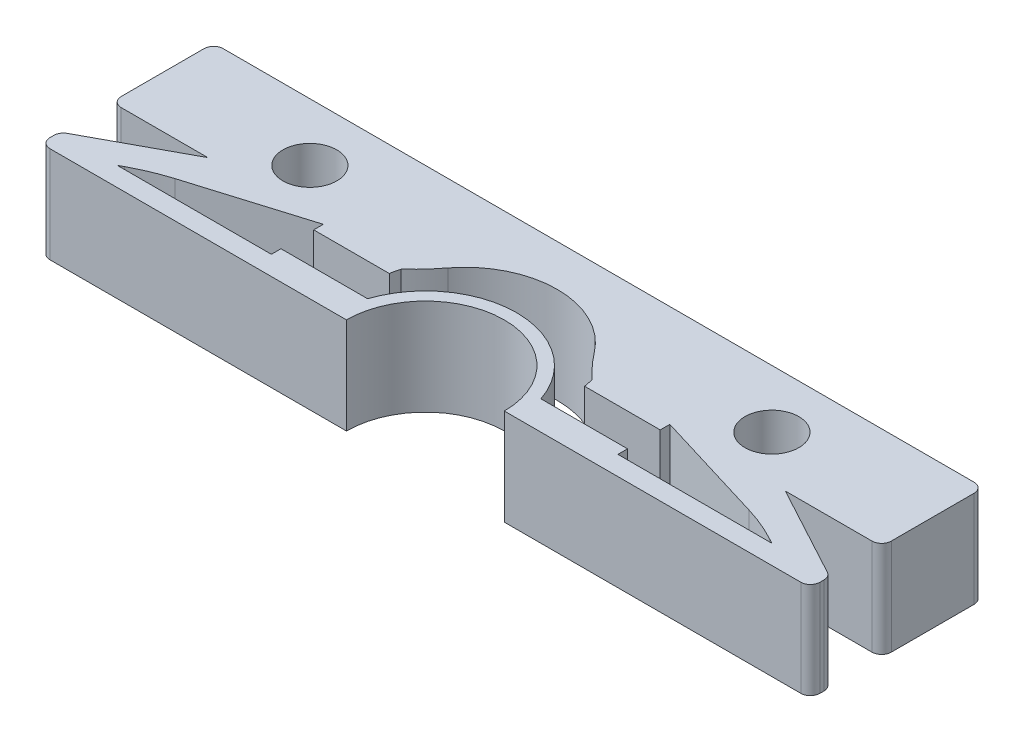
SolidWorks part; units mm, degrees
ref_plane "Front Plane" through (0, 0, 0) normal (0, 0, 1) x (1, 0, 0)
ref_plane "Top Plane" through (0, 0, 0) normal (0, 1, 0) x (1, 0, 0)
ref_plane "Right Plane" through (0, 0, 0) normal (1, 0, 0) x (0, 0, -1)
sketch "Sketch1" plane through (0, 0, 0) normal (0, 1, 0) x (1, 0, 0)
  line L0 (0, 0) -> (0, 9)
  line L1 (0, 9) -> (40, 9)
  line L2 (40, 9) -> (40, 0)
  line L3 (0, 0) -> (16, 0)
  line L4 (16, 0) -> (16, 5)
  line L5 (16, 5) -> (24, 5)
  line L6 (24, 5) -> (24, 0)
  line L7 (24, 0) -> (40, 0)
  dimension "D1" = 40
  dimension "D2" = 9
  dimension "D3" = 9
  dimension "D4" = 16
  dimension "D5" = 16
  dimension "D6" = 5
extrude "Boss-Extrude1" add sketch "Sketch1" along normal blind 5
sketch "Sketch2" plane through (0, 5, 0) normal (0, 1, 0) x (1, 0, 0)
  line L0 (0, 9) -> (8, 9)
  line L1 (40, 9) -> (0, 9) construction
  line L2 (8, 9) -> (8, 6)
  line L3 (8, 6) -> (32, 6)
  line L4 (0, 0) -> (0, 3.7) construction
  line L5 (0, 9) -> (0, 0) construction
  line L6 (0, 3.7) -> (19.4811, 3.7) construction
  line L7 (0, 3.7) -> (5, 3.7)
  line L8 (5, 3.7) -> (8, 3.7)
  line L9 (0, 0) -> (0, 1)
  line L10 (5, 3.7) -> (0, 1)
  line L11 (0, 1) -> (0, 3.7)
  line L12 (0, 1) -> (3, 1)
  line L13 (3, 1) -> (8, 3.7)
  line L14 (0, 1) -> (12.9505, 1) construction
  line L15 (16, 1) -> (13, 1)
  line L16 (16, 0) -> (16, 5) construction
  line L17 (8, 3.7) -> (11, 3.7)
  line L18 (8, 3.7) -> (13, 1)
  line L19 (11, 3.7) -> (16, 1)
  line L20 (24, 1) -> (27, 1)
  line L21 (24, 5) -> (24, 0) construction
  line L22 (40, 3.7) -> (35, 3.7)
  line L23 (40, 0) -> (40, 9) construction
  line L24 (35, 3.7) -> (32, 3.7)
  line L25 (32, 3.7) -> (29, 3.7)
  line L26 (24, 1) -> (29, 3.7)
  line L27 (27, 1) -> (32, 3.7)
  line L28 (40, 1) -> (37, 1)
  line L29 (32, 3.7) -> (37, 1)
  line L30 (35, 3.7) -> (40, 1)
  line L31 (3, 1) -> (13, 1)
  line L32 (11, 3.7) -> (16, 3.7)
  line L33 (16, 3.7) -> (16, 1)
  line L34 (24, 1) -> (24, 3.7)
  line L35 (24, 3.7) -> (29, 3.7)
  line L36 (27, 1) -> (37, 1)
  line L37 (40, 1) -> (40, 3.7)
  circle A0 centre (8, 6) radius 1.4
  circle A1 centre (32, 6) radius 1.4
  line M5 (16, 0) -> (16, 5)
  line M7 (24, 5) -> (24, 0)
  line M9 (40, 0) -> (40, 9)
  line M11 (0, 9) -> (0, 0)
  dimension "D2" = 2.8
  dimension "D4" = 2.8
  dimension "D1" = 8
  dimension "D3" = 24
  dimension "D5" = 3
  dimension "D6" = 3.7
  dimension "D7" = 1
  dimension "D8" = 5
  dimension "D9" = 3
  dimension "D10" = 3
  dimension "D11" = 3
  dimension "D12" = 3
  dimension "D13" = 3
  dimension "D14" = 5
  dimension "D15" = 3
  dimension "D16" = 3
  dimension "D17" = 3
extrude "Cut-Extrude1" cut sketch "Sketch2" along normal blind 5 and the other way blind 10 contours L2 A0 L3 | L3 A0 L2 | A1 | L35 L26 M7 | L27 L36 L29 | L22 L30 M9 | L10 L7 M11 | L13 L31 L18 | L32 L19 M5 region at (32, 5, -7.3604) region at (8.5942, 5, -6.5942) region at (7.8019, 5, -5.8019) region at (1.6667, 5, -2.8) region at (8, 5, -1.9) region at (14.3333, 5, -2.8) region at (25.6667, 5, -2.8) region at (32, 5, -1.9) region at (38.3333, 5, -2.8)
fillet "Fillet1" radius 10 2 edges at (32, 2.5, -3.7) (8, 2.5, -3.7)
fillet "Fillet2" radius 0.5 16 edges at (40, 2.5, -9) (0, 2.5, -9) (0, 2.5, -3.7) (0, 2.5, -1) (0, 2.5, 0) (24, 2.5, -5) (16, 2.5, -5) (16, 2.5, -1) (16, 2.5, 0) (16, 2.5, -3.7) (24, 2.5, -3.7) (24, 2.5, -1) (24, 2.5, 0) (40, 2.5, 0) (40, 2.5, -1) (40, 2.5, -3.7)
sketch "Sketch3" plane through (0, 5, 0) normal (0, 1, 0) x (1, 0, 0)
  line L0 (13, 1) -> (8, 2.3351)
  line L3 (11, 3.7) -> (16.2683, 2.2932)
  line L4 (16.2683, 2.2932) -> (16.4305, 1)
  line L5 (13, 1) -> (16.4305, 1)
  line L6 (8, 2.3351) -> (11, 3.7)
  line L7 (20, 5) -> (20, -2.2674)
  line L8 (16.5, 5) -> (23.5, 5) construction
  line L10 (32, 2.3351) -> (29, 3.7)
  line L11 (27, 1) -> (32, 2.3351)
  line L12 (27, 1) -> (23.5695, 1)
  line L13 (23.7317, 2.2932) -> (23.5695, 1)
  line L14 (29, 3.7) -> (23.7317, 2.2932)
  arc A0 (12.7515, 1.1342) -> (3.2485, 1.1342) centre (8, -7.6649) ccw construction
sketch "Sketch4" plane through (0, 5, 0) normal (0, 1, 0) x (1, 0, 0)
  line L0 (10.4832, 1) -> (8, 2.3351)
  line L3 (11, 3.7) -> (16.0217, 1)
  line L5 (10.4832, 1) -> (16.0217, 1)
  line L7 (20, 5) -> (20, -2.2674)
  line L8 (24.5, 3.7) -> (29, 3.7) construction
  line L9 (24.2624, 1.1417) -> (29, 3.7) construction
  line L11 (29.5168, 1) -> (32, 2.3351)
  line L12 (29.5168, 1) -> (23.9783, 1)
  line L14 (29, 3.7) -> (23.9783, 1)
  line L15 (29, 3.7) -> (34.9239, 1.8981)
  line L16 (34.9239, 1.8981) -> (32, 2.3351)
  line L17 (11, 3.7) -> (5.0761, 1.8981)
  line L18 (5.0761, 1.8981) -> (8, 2.3351)
  arc A0 (36.7515, 1.1342) -> (27.2485, 1.1342) centre (32, -7.6649) ccw construction
  arc A1 (12.7515, 1.1342) -> (3.2485, 1.1342) centre (8, -7.6649) ccw construction
  line M74 (29, 3.7) -> (24.2624, 1.1417)
  arc M75 (24.2624, 1.1417) -> (24, 0.7018) centre (24.5, 0.7018) ccw
  line M102 (27, 1) -> (27.2485, 1.1342)
  arc M103 (27.2485, 1.1342) -> (36.7515, 1.1342) centre (32, -7.6649) cw
extrude "Cut-Extrude3" cut sketch "Sketch4" against normal blind 7 contours L12 M102 M103 M74 M75 | L0 L18 L17 L3 L5 region at (28.4526, 5, -2.2688) body kept at (15.5, 0, 0)
ref_plane "Mirror plane" through (0, 0, -2.35) normal (0, 0, 1) x (1, 0, 0)
sketch "Sketch6" plane through (0, 0, -3.7) normal (0, 0, 1) x (1, 0, 0)
  line L0 (29, 0) -> (29, 5) construction
  line L1 (11, 5) -> (15.5, 5)
  line L2 (11, 5) -> (11, 0)
  line L3 (11, 0) -> (15.5, 0)
  line L4 (15.5, 5) -> (15.5, 0)
  line L5 (24.5, 5) -> (29, 5)
  line L6 (24.5, 5) -> (24.5, 0)
  line L7 (24.5, 0) -> (29, 0)
  line L8 (29, 5) -> (29, 0)
extrude "Boss-Extrude2" add sketch "Sketch6" along normal blind 0.5
mirror "Mirror1" about plane through (0, 0, -2.35) normal (0, 0, 1) of "Boss-Extrude2"
sketch "Sketch7" plane through (0, 5, 0) normal (0, 1, 0) x (1, 0, 0)
  line L1 (15.5, 1) -> (24.5, 1)
  line L2 (15.5, 1) -> (15.5, 0)
  line L3 (15.5, 0) -> (24.5, 0)
  line L4 (24.5, 1) -> (24.5, 0)
extrude "Boss-Extrude3" add sketch "Sketch7" along direction (0, -1, 0) on the side against the normal up to surface (5 mm away) up to face at (32, 0, -4.6)
sketch "Sketch9" plane through (0, 5, 0) normal (0, 1, 0) x (1, 0, 0)
  line L0 (0.5, 0) -> (39.5, 0) construction
  line L2 (24.1, 0) -> (24.7434, 0)
  line L3 (15.9, 0) -> (15.2566, 0)
  line L4 (15.9, 0) -> (24.1, 0)
  arc A1 (24.1, 0) -> (15.9, 0) centre (20, 0) ccw
  arc A4 (24.7434, 0) -> (15.2566, 0) centre (20, 0) ccw
  line M21 (24.5, 1) -> (15.5, 1)
  line M22 (15.5, 1) -> (15.5, 1.5)
  line M48 (24.5, 1.5) -> (24.5, 1)
  dimension "D1" = 0.6434
sketch "Sketch10" plane through (0, 5, 0) normal (0, 1, 0) x (1, 0, 0)
  line L0 (24.5, 2.35) -> (25.1434, 2.35) construction
  line L1 (24.1, 0) -> (24.7434, 0) construction
  line L2 (14.8566, 2.35) -> (15.5, 2.35)
  line L3 (15.5, 3.7) -> (16.0311, 3.7)
  line L4 (15.5, 3.2) -> (11, 3.2) construction
  line L5 (26.403, 3.2) -> (26.403, 1.5) construction
  line L6 (29, 3.2) -> (24.5, 3.2) construction
  line L7 (29, 1.5) -> (24.5, 1.5) construction
  line L8 (26.403, 2.35) -> (22.5949, 2.35) construction
  line L9 (24.5, 3.7) -> (25.0727, 3.7)
  line L10 (24.5, 3.7) -> (24.5, 3.2)
  line L11 (24.5, 3.2) -> (25.0727, 3.2)
  line L12 (25.0727, 3.7) -> (25.0727, 3.2)
  line L13 (15.5, 3.7) -> (14.9273, 3.7)
  line L14 (15.5, 3.7) -> (15.5, 3.2)
  line L15 (15.5, 3.2) -> (14.9273, 3.2)
  line L16 (14.9273, 3.7) -> (14.9273, 3.2)
  line L17 (16.0311, 3.7) -> (16.5, 5)
  line L18 (16.5, 5) -> (23.3195, 5)
  line L19 (16.5, 5) -> (23.5, 5) construction
  line L20 (23.3195, 5) -> (24.1953, 3.7)
  line L21 (24.1953, 3.7) -> (24.5, 3.7)
  line L22 (24.1953, 3.7) -> (24.5, 3.7)
  arc A1 (25.1434, 2.35) -> (14.8566, 2.35) centre (20, 2.35) ccw
  arc A2 (15.5, 3.7) -> (24.5, 3.7) centre (20, 2.0607) cw
  line M31 (11, 3.2) -> (15.5, 3.2)
  line M32 (15.5, 3.2) -> (15.5, 3.7)
  arc M33 (15.5, 3.7) -> (16, 4.2) centre (15.5, 4.2) ccw
  line M34 (16, 4.2) -> (16, 4.5)
  arc M35 (16, 4.5) -> (16.5, 5) centre (16.5, 4.5) cw
  line M36 (16.5, 5) -> (23.5, 5)
  arc M37 (23.5, 5) -> (24, 4.5) centre (23.5, 4.5) cw
  line M38 (24, 4.5) -> (24, 4.2)
  arc M39 (24, 4.2) -> (24.5, 3.7) centre (24.5, 4.2) ccw
  line M40 (24.5, 3.7) -> (24.5, 3.2)
  line M41 (24.5, 3.2) -> (29, 3.2)
extrude "Boss-Extrude4" add sketch "Sketch9" against normal up to surface (5 mm away) contours A4 A1 M48 M22 M21 region at (20, 5, -4.1975) up to face at (20, 0, -3.4862)
sketch "Sketch11" plane through (0, 0, 0) normal (0, 1, 0) x (1, 0, 0)
  line L0 (0.5, 0) -> (39.5, 0) construction
  circle A0 centre (20, 0) radius 4.1
extrude "Cut-Extrude5" cut sketch "Sketch11" along normal up to surface (5 mm away) up to face at (20, 5, -2.55)
ref_plane "Plane2" through (24.5, 5, -1.5) normal (-0.3162, 0, -0.9487) x (-0.9487, 0, 0.3162)
extrude "Cut-Extrude7" cut sketch "Sketch10" against normal blind 5 contours A2 M33 M34 M35 M36 M37 M38 M39 | A1 L9 M41 M40 | L13 A1 M31 M32 | L3 L17 M35 M34 M33 | L20 L21 M39 M38 M37 M36 region at (16.1326, 5, -4.374) region at (15.2379, 5, -3.4413) region at (20, 5, -5.6796) region at (24.7621, 5, -3.4413) region at (23.7849, 5, -4.5579)
fillet "Fillet3" radius 10 2 edges at (15.5, 2.5, -3.7) (24.5, 2.5, -3.7)
